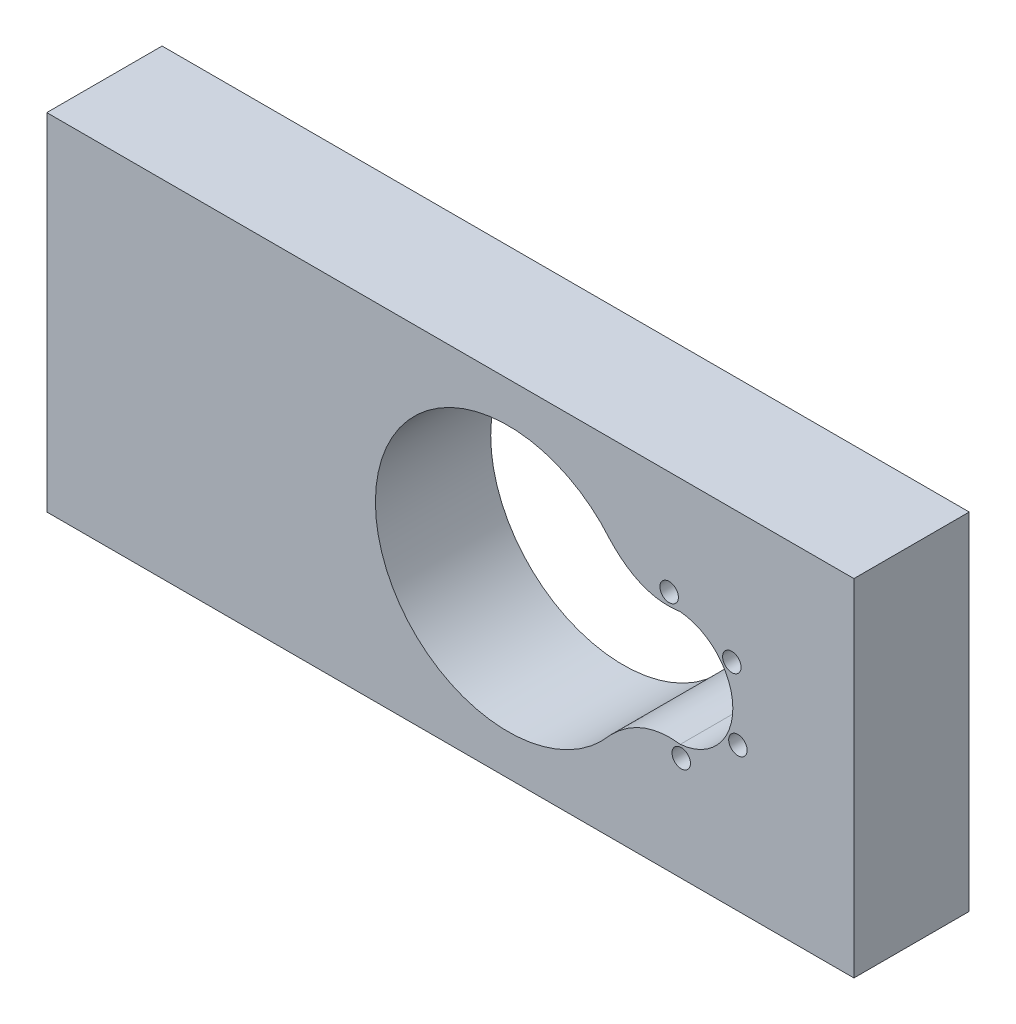
SolidWorks part; units mm, degrees
ref_plane "Plan de face" through (0, 0, 0) normal (0, 0, 1) x (1, 0, 0)
ref_plane "Plan de dessus" through (0, 0, 0) normal (0, 1, 0) x (1, 0, 0)
ref_plane "Plan de droite" through (0, 0, 0) normal (1, 0, 0) x (0, 0, -1)
sketch "Esquisse1" plane through (0, 0, 0) normal (0, 0, 1) x (1, 0, 0)
  line L1 (0, 0) -> (70, 0)
  line L2 (0, 0) -> (0, 30)
  line L3 (0, 30) -> (70, 30)
  line L4 (70, 0) -> (70, 30)
  dimension "D1" = 30
  dimension "D2" = 70
extrude "Boss.-Extru.1" add sketch "Esquisse1" along normal blind 10
sketch "Esquisse2" plane through (0, 0, 10) normal (0, 0, 1) x (1, 0, 0)
  line L0 (66.0915, 15) -> (-1.5751, 15) construction
  line L1 (54.5, 34.4565) -> (54.5, -6.8023) construction
  line L2 (70, 30) -> (0, 30) construction
  line L4 (0, 30) -> (0, 0) construction
  arc A0 (54.9408, 19.9805) -> (54.9408, 10.0195) centre (54.5, 15) cw
  circle A2 centre (53.9746, 20.9769) radius 0.8
  circle A3 centre (59.4135, 18.4435) radius 0.8
  circle A4 centre (59.9389, 12.4666) radius 0.8
  circle A5 centre (55.0254, 9.0231) radius 0.8
  arc A6 (48.86, 22.3315) -> (48.86, 7.6685) centre (40, 15) ccw
  circle A8 centre (49.0611, 17.5334) radius 0.8 [skipped]
  circle A9 centre (49.5865, 11.5565) radius 0.8 [skipped]
  spline S0 degree 2 poles (48.86, 22.3315) (51.5345, 19.4593) (54.9408, 19.9805) knots 0 0 0 1 1 1
  spline S1 degree 2 poles (48.86, 7.6685) (51.5403, 10.446) (54.9408, 10.0195) knots 0 0 0 1 1 1
  point P15 (0, 0)
  point P18 (54.5, 15)
  point P23 (0, 0)
  point P32 (59.5, 15)
  dimension "D1" = 11.5
  dimension "D2" = 5
  dimension "D3" = 1.6
  dimension "D5" = 14.5
  dimension "D8" = 10.64
  dimension "D6" = 15
  dimension "D7" = 40
  dimension "D9" = 10.64
  dimension "D10" = 8.86
  dimension "D11" = 4.7
  dimension "D12" = 4.7
  dimension "D13" = 5.9769
  dimension "D14" = 6
  dimension "D4" = 6
extrude "Enlèv. mat.-Extru.1" cut sketch "Esquisse2" against normal through all
